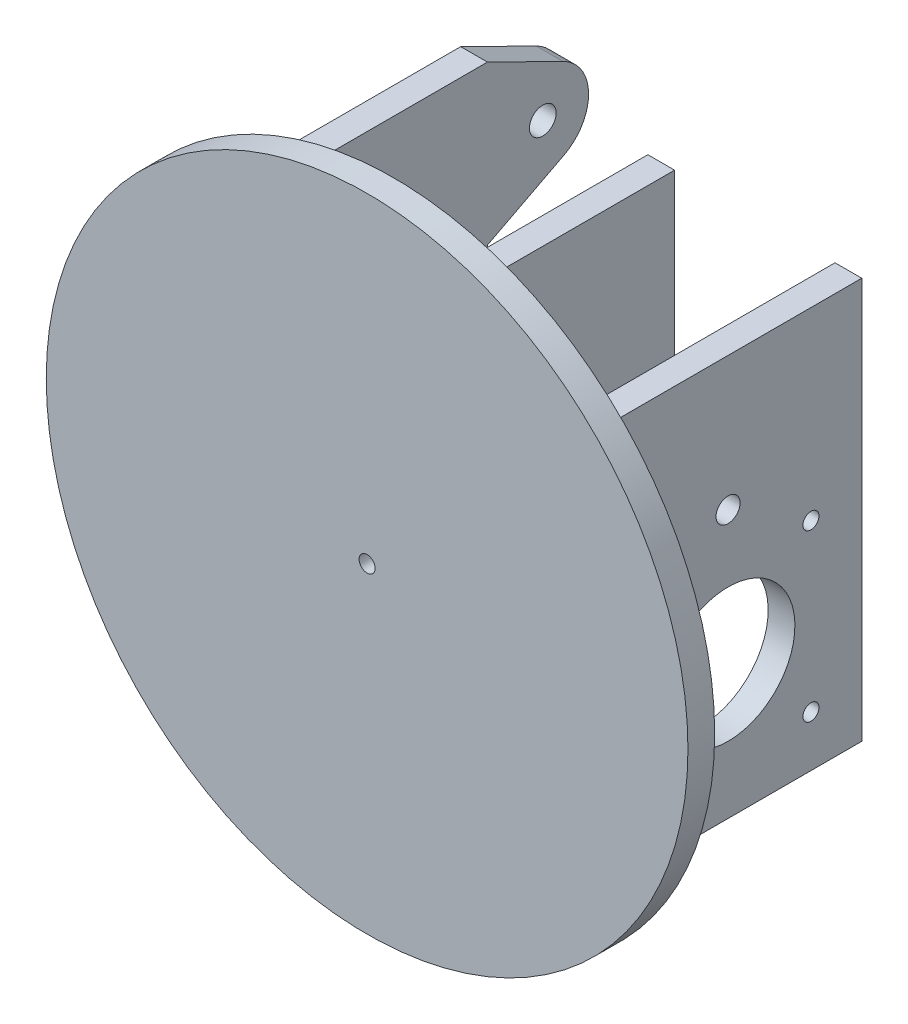
SolidWorks part; units mm, degrees
ref_plane "Front Plane" through (0, 0, 0) normal (0, 0, 1) x (1, 0, 0)
ref_plane "Top Plane" through (0, 0, 0) normal (0, 1, 0) x (1, 0, 0)
ref_plane "Right Plane" through (0, 0, 0) normal (1, 0, 0) x (0, 0, -1)
sketch "Sketch1" plane through (0, 0, 0) normal (0, 0, 1) x (1, 0, 0)
  circle A0 centre (0, 0) radius 60
  circle A1 centre (0, 0) radius 1.5
  dimension "D1" = 120
  dimension "D2" = 3
extrude "Boss-Extrude1" add sketch "Sketch1" along normal blind 5
sketch "Sketch2" plane through (0, 0, 0) normal (0, 0, -1) x (-1, 0, 0)
  line L0 (37.5, 37.5) -> (-37.5, -37.5) construction
  line L1 (-37.5, 37.5) -> (37.5, -37.5) construction
  line L3 (-37.5, 37.5) -> (-32.5, 37.5)
  line L4 (-37.5, 37.5) -> (-37.5, -37.5)
  line L5 (-37.5, -37.5) -> (-32.5, -37.5)
  line L6 (-32.5, 37.5) -> (-32.5, -37.5)
  line L7 (37.5, 37.5) -> (32.5, 37.5)
  line L8 (37.5, 37.5) -> (37.5, -37.5)
  line L9 (37.5, -37.5) -> (32.5, -37.5)
  line L10 (32.5, 37.5) -> (32.5, -37.5)
  line L11 (-2.5, -37.5) -> (2.5, -37.5)
  line L12 (-2.5, -37.5) -> (-2.5, 37.5)
  line L13 (-2.5, 37.5) -> (2.5, 37.5)
  line L14 (2.5, -37.5) -> (2.5, 37.5)
  line L15 (-2.5, -37.5) -> (2.5, 37.5) construction
  line L16 (-2.5, 37.5) -> (2.5, -37.5) construction
  point P7 (0, 0)
  dimension "D1" = 75
  dimension "D2" = 5
extrude "Boss-Extrude2" add sketch "Sketch2" along normal blind 50
sketch "Sketch3" plane through (32.5, 0, 0) normal (-1, 0, 0) x (0, 0, 1)
  line L0 (-50, -37.5) -> (0, 12.5) construction
  line L1 (-50, -37.5) -> (-50, 37.5) construction
  line L2 (-50, -37.5) -> (0, -37.5) construction
  line L3 (0, -37.5) -> (0, 37.5) construction
  line L4 (0, -37.5) -> (-50, 12.5) construction
  circle A0 centre (-40.5, 3) radius 1.5
  circle A1 centre (-9.5, 3) radius 1.5
  circle A2 centre (-9.5, -28) radius 1.5
  circle A3 centre (-40.5, -28) radius 1.5
  circle A4 centre (-25, -12.5) radius 12.5
  dimension "D2" = 3
  dimension "D4" = 25
  dimension "D1" = 45
  dimension "D3" = 31
extrude "Cut-Extrude1" cut sketch "Sketch3" against normal through all
sketch "Sketch5" plane through (-2.5, 0, 0) normal (-1, 0, 0) x (0, 0, 1)
  line L0 (-25, -37.5) -> (-25, 37.5) construction
  line L1 (-50, -37.5) -> (0, -37.5) construction
  line L2 (-50, 37.5) -> (0, 37.5) construction
  line L4 (-23.4125, -14.0875) -> (-26.5875, -14.0875)
  line L5 (-23.4125, -14.0875) -> (-23.4125, -10.9125)
  line L6 (-23.4125, -10.9125) -> (-26.5875, -10.9125)
  line L7 (-26.5875, -14.0875) -> (-26.5875, -10.9125)
  line L8 (-23.4125, -14.0875) -> (-26.5875, -10.9125) construction
  line L9 (-23.4125, -10.9125) -> (-26.5875, -14.0875) construction
  circle A0 centre (-25, -12.5) radius 2.2451
  circle A1 centre (-25, 12.5) radius 2.2451
  dimension "D3" = 3.175
  dimension "D1" = 25
  dimension "D2" = 25
extrude "Cut-Extrude4" cut sketch "Sketch5" against normal blind 53 and the other way through all contours A1 region at (-2.5, 12.5, -25)
sketch "Sketch6" plane through (-37.5, 0, 0) normal (-1, 0, 0) x (0, 0, 1)
  line L0 (-50, -37.5) -> (0, 12.5) construction
  line L1 (0, -37.5) -> (-50, 12.5) construction
  circle A0 centre (-40.5, 3) radius 1.5
  circle A1 centre (-9.5, 3) radius 1.5
  circle A2 centre (-9.5, -28) radius 1.5
  circle A3 centre (-40.5, -28) radius 1.5
  circle A4 centre (-25, -12.5) radius 12.5
  dimension "D1" = 3
  dimension "D3" = 25
  dimension "D2" = 31
extrude "Cut-Extrude5" cut sketch "Sketch6" against normal up to surface (5 mm away) up to face at (-32.5, 10.2549, -25)
sketch "Sketch7" plane through (-37.5, 0, 0) normal (-1, 0, 0) x (0, 0, 1)
  line L0 (-25, -12.5) -> (-60.3553, 22.8553) construction
  line L1 (0, 60) -> (0, -60) construction
  line L2 (-50, 37.5) -> (-64.1385, 30.5347)
  line L3 (-64.2907, 15.2528) -> (-50, 7.8553)
  line L4 (-50, -37.5) -> (-50, 37.5) construction
  line L6 (-50, 7.8553) -> (-50, 37.5)
  circle A2 centre (-25, -12.5) radius 12.5 construction
  circle A3 centre (-60.3553, 22.8553) radius 2.5
  arc A4 (-64.2907, 15.2528) -> (-64.1385, 30.5347) centre (-60.3553, 22.8553) cw
  dimension "D3" = 5
  dimension "D1" = 50
  dimension "D2" = 45
  dimension "D4" = 15
extrude "Boss-Extrude4" add sketch "Sketch7" against normal blind 5
sketch "Sketch8" plane through (-37.5, 0, 0) normal (-1, 0, 0) x (0, 0, 1)
  line L0 (-25, -12.5) -> (-25, 22.8553) construction
  line L1 (-25, 22.8553) -> (-60.3553, 22.8553) construction
